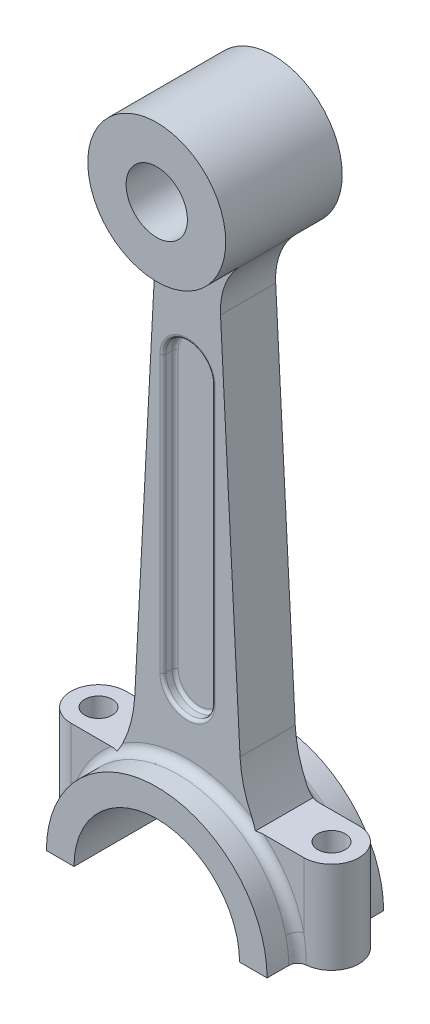
SolidWorks part; units mm, degrees
ref_plane "Front Plane" through (0, 0, 0) normal (0, 0, 1) x (1, 0, 0)
ref_plane "Top Plane" through (0, 0, 0) normal (0, 1, 0) x (1, 0, 0)
ref_plane "Right Plane" through (0, 0, 0) normal (1, 0, 0) x (0, 0, -1)
sketch "Sketch1" plane through (0, 0, 0) normal (0, 0, 1) x (1, 0, 0)
  line L0 (0, 97.4394) -> (0, -103.7606) construction
  line L1 (-121.6419, 0) -> (128.9405, 0) construction
  line L2 (-10.1976, 77.3831) -> (-18.0588, -72.6177)
  line L3 (10.1976, 77.3831) -> (18.0588, -72.6177)
  circle A0 centre (0, -103.7606) radius 27
  circle A1 centre (0, -103.7606) radius 36
  circle A2 centre (0, 97.4394) radius 22.5
  circle A3 centre (0, 97.4394) radius 10
  dimension "D1" = 45
  dimension "D2" = 20
  dimension "D3" = 72
  dimension "D4" = 54
  dimension "D5" = 201.2
  dimension "D6" = 6
sketch "Sketch2" plane through (0, 0, 0) normal (0, 0, 1) x (1, 0, 0)
  line L0 (0, 97.4394) -> (0, -103.7606) construction
  line L1 (-121.6419, 0) -> (128.9405, 0) construction
  line L2 (-10.1976, 77.3831) -> (-18.0588, -72.6177)
  line L3 (10.1976, 77.3831) -> (18.0588, -72.6177)
  circle A0 centre (0, -103.7606) radius 27
  circle A1 centre (0, -103.7606) radius 36
  circle A2 centre (0, 97.4394) radius 22.5
  circle A3 centre (0, 97.4394) radius 16.9
  dimension "D1" = 45
  dimension "D2" = 33.8
  dimension "D3" = 72
  dimension "D4" = 54
  dimension "D5" = 201.2
  dimension "D6" = 6
extrude "Boss-Extrude1" add sketch "Sketch1" along normal mid plane 38 contours A1 A0 | A2 A3 region at (-11.4317, 116.0763, 0) region at (0, -68.7788, 0)
extrude "Boss-Extrude2" add sketch "Sketch2" along normal mid plane 18 contours A2 L2 A1 L3 region at (0, -3.3198, 0)
sketch "Sketch4" plane through (0, 0, 9) normal (0, 0, 1) x (1, 0, 0)
  line L0 (0, 45) -> (0, -45) construction
  line L1 (8, 45) -> (8, -45)
  line L2 (-8, 45) -> (-8, -45)
  arc A0 (8, 45) -> (-8, 45) centre (0, 45) ccw
  arc A1 (-8, -45) -> (8, -45) centre (0, -45) ccw
  point P2 (0, 0)
  dimension "D2" = 8
  dimension "D1" = 90
extrude "Cut-Extrude1" cut sketch "Sketch4" against normal blind 4
mirror "Mirror1" about plane through (0, 0, 0) normal (0, 0, 1) of "Cut-Extrude1"
fillet "Fillet1" radius 1 16 edges at (0, 53, -9) (8, 0, -9) (0, -53, -9) (0, 53, -5) (8, 0, -5) (0, -53, -5) (0, 53, 5) (8, 0, 5) (0, -53, 5) (0, 53, 9) (8, 0, 9) (0, -53, 9) (-8, 0, -9) (-8, 0, -5) (-8, 0, 5) (-8, 0, 9)
sketch "Sketch5" plane through (0, 0, 19) normal (0, 0, 1) x (1, 0, 0)
  line L1 (-36, -103.7606) -> (36, -103.7606)
  arc A2 (-36, -103.7606) -> (36, -103.7606) centre (0, -103.7606) ccw
  circle A3 centre (0, -103.7606) radius 36 construction
extrude "Cut-Extrude4" cut sketch "Sketch5" against normal through all
ref_plane "Plane1" through (0, -73.7606, 0) normal (0, -1, 0) x (-1, 0, 0)
fillet "Fillet3" radius 40 2 edges at (18.0588, -72.6177, 0) (-18.0588, -72.6177, 0)
sketch "Sketch6" plane through (0, -73.7606, 0) normal (0, -1, 0) x (-1, 0, 0)
  line L0 (-38, 0) -> (38, 0) construction
  line L1 (-38, 9) -> (38, 9)
  line L2 (-38, -9) -> (38, -9)
  arc A0 (-38, 9) -> (-38, -9) centre (-38, 0) ccw
  arc A1 (38, -9) -> (38, 9) centre (38, 0) ccw
  point P2 (0, 0)
  dimension "D2" = 9
  dimension "D1" = 76
extrude "Boss-Extrude3" add sketch "Sketch6" along normal up to surface (30 mm away) up to face at (-31.5, -103.7606, 0)
sketch "Sketch7" plane through (0, 0, 9) normal (0, 0, 1) x (1, 0, 0)
  line L1 (-27, -103.7606) -> (27, -103.7606)
  line L2 (-27, -103.7606) -> (27, -103.7606)
  arc A1 (27, -103.7606) -> (-27, -103.7606) centre (0, -103.7606) ccw
  arc A2 (27, -103.7606) -> (-27, -103.7606) centre (0, -103.7606) ccw
  dimension "D1" = 0
extrude "Cut-Extrude5" cut sketch "Sketch7" against normal through all
sketch "Sketch8" plane through (0, -73.7606, 0) normal (0, 1, 0) x (1, 0, 0)
  circle A0 centre (38, 0) radius 4.5
  circle A1 centre (-38, 0) radius 4.5
extrude "Cut-Extrude6" cut sketch "Sketch8" against normal through all
fillet "Fillet2" radius 22.5 2 edges at (10.1976, 77.3831, 0) (-10.1976, 77.3831, 0)
fillet "Fillet4" radius 3 2 edges at (0, -67.7606, -9) (0, -67.7606, 9)
